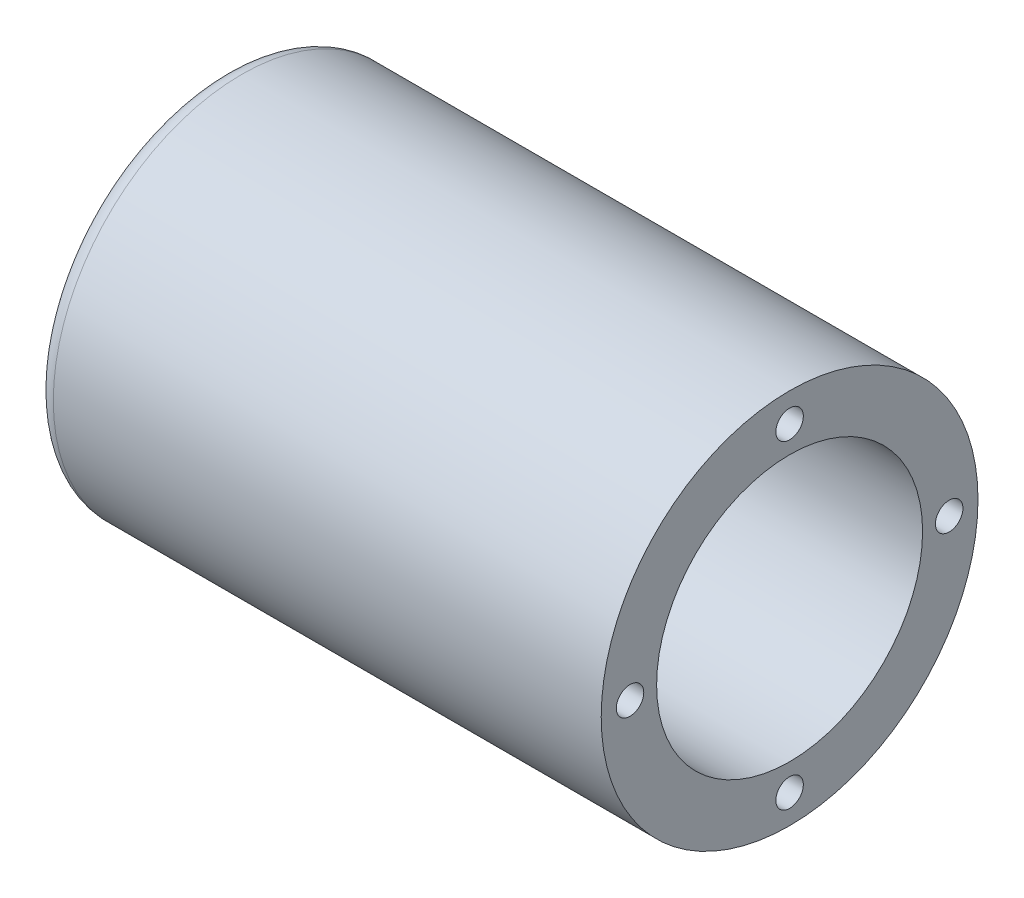
SolidWorks part; units mm, degrees
material "Custom PLA"
ref_plane "Front Plane" through (0, 0, 0) normal (0, 0, 1) x (1, 0, 0)
ref_plane "Top Plane" through (0, 0, 0) normal (0, 1, 0) x (1, 0, 0)
ref_plane "Right Plane" through (0, 0, 0) normal (1, 0, 0) x (0, 0, -1)
sketch "Sketch1" plane through (0, 0, 0) normal (0, 0, 1) x (1, 0, 0)
  line L0 (-31.9, 0) -> (31.9, 0)
  line L1 (-31.9, 0) -> (-31.9, 21.25)
  line L2 (-31.9, 21.25) -> (31.9, 21.25)
  line L7 (31.9, 21.25) -> (31.9, 0)
  point P3 (0, 0)
  dimension "D1" = 63.8
  dimension "D2" = 21.25
revolve "Revolve1" add sketch "Sketch1" angle 360 about L0
sketch "Sketch2" plane through (31.9, 0, 0) normal (1, 0, 0) x (0, 0, -1)
  circle A0 centre (0, 0) radius 15
  dimension "D1" = 30
extrude "Cut-Extrude1" cut sketch "Sketch2" against normal blind 61.3
sketch "Sketch3" plane through (31.9, 0, 0) normal (1, 0, 0) x (0, 0, -1)
  line L0 (0, 21.25) -> (0, -21.25) construction
  line L1 (-21.25, 0) -> (21.25, 0) construction
  circle A0 centre (0, 0) radius 18 construction
  circle A1 centre (0, 0) radius 21.25 construction
  circle A2 centre (0, 18) radius 1.55
  dimension "D1" = 36
  dimension "D2" = 3.1
extrude "Cut-Extrude2" cut sketch "Sketch3" against normal blind 3.8
pattern_circular "CirPattern1" count 4 over 360 about axis through (31.9, 0, 0) along (-1, 0, 0) of "Cut-Extrude2"
sketch "Sketch4" plane through (-29.4, 0, 0) normal (1, 0, 0) x (0, 0, -1)
  circle A0 centre (0, 0) radius 12 construction
  circle A1 centre (0, 12) radius 1.8
  dimension "D1" = 24
  dimension "D2" = 3.6
extrude "Cut-Extrude3" cut sketch "Sketch4" against normal up to next
pattern_circular "CirPattern2" count 4 over 360 about axis through (-29.4, 0, 0) along (1, 0, 0) of "Cut-Extrude3"
ref_axis "Axis1" through (33, 0, 0) along (-1, 0, 0)
ref_plane "Plane1" through (0, 0, -21.25) normal (0, 0, -1) x (-1, 0, 0)
sketch "Sketch5" plane through (0, 0, -21.25) normal (0, 0, -1) x (-1, 0, 0)
  line L1 (-20, 20) -> (20, 20)
  line L2 (-20, 20) -> (-20, -20)
  line L3 (-20, -20) -> (20, -20)
  line L4 (20, 20) -> (20, -20)
  line L5 (-20, 20) -> (20, -20) construction
  line L6 (-20, -20) -> (20, 20) construction
  point P0 (0, 0)
  dimension "D1" = 40
  dimension "D2" = 40
extrude "Boss-Extrude1" [suppressed] add sketch "Sketch5" along normal blind 5 and the other way up to surface
ref_plane "Plane2" [suppressed] through (-25, 0, 0) normal (-1, 0, 0) x (0, 0, 1)
ref_plane "Plane3" [suppressed] through (0, 0, -56.25) normal (0, 0, -1) x (-1, 0, 0)
sketch "Sketch7" [suppressed] plane through (-20, 0, 0) normal (-1, 0, 0) x (0, 0, 1)
  line L1 (-26.25, 20) -> (-19.25, 20)
  line L2 (-26.25, 20) -> (-26.25, -20)
  line L3 (-26.25, -20) -> (-19.25, -20)
  line L4 (-19.25, 20) -> (-19.25, -20)
  line L5 (-26.25, -20) -> (-7.1807, -20) construction
  dimension "D1" = 7
sketch "Sketch8" [suppressed] plane through (0, 0, -56.25) normal (0, 0, -1) x (-1, 0, 0)
  line L0 (25, -11) -> (25, 11) construction
  line L1 (25, 20) -> (32, 20)
  line L2 (25, 20) -> (25, -20)
  line L3 (25, -20) -> (32, -20)
  line L4 (32, 20) -> (32, -20)
  line L5 (-33, 0) -> (33, 0) construction
  point P6 (25, 0)
  dimension "D1" = 7
  dimension "D2" = 40
loft "Loft1" [suppressed] add profiles "Sketch7", "Sketch8" start constraint normal to profile start tangent length 0.8 end constraint normal to profile end tangent length 1.4
mirror "Mirror1" [suppressed] about plane through (0, 0, 0) normal (1, 0, 0)
fillet "Fillet1" radius 2 1 edges at (-31.9, -21.25, 0)
